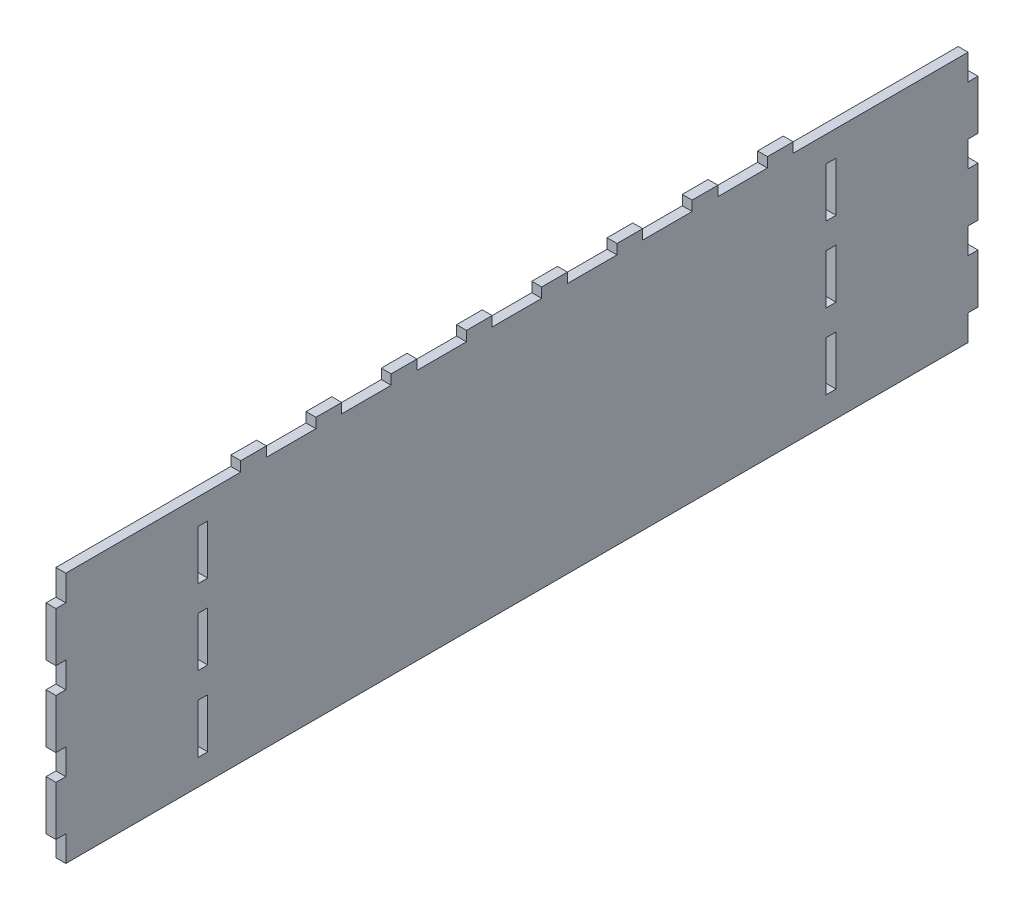
SolidWorks part; units mm, degrees
material "ENPH 253 Hardboard"
ref_plane "Front Plane" through (0, 0, 0) normal (0, 0, 1) x (1, 0, 0)
ref_plane "Top Plane" through (0, 0, 0) normal (0, 1, 0) x (1, 0, 0)
ref_plane "Right Plane" through (0, 0, 0) normal (1, 0, 0) x (0, 0, -1)
sketch "Sketch1" plane through (0, 0, 0) normal (1, 0, 0) x (0, 0, -1)
  line L1 (-139.7, 38.1) -> (139.7, 38.1)
  line L2 (-139.7, 38.1) -> (-139.7, -38.1)
  line L3 (-139.7, -38.1) -> (139.7, -38.1)
  line L4 (139.7, 38.1) -> (139.7, -38.1)
  line L5 (-139.7, 38.1) -> (139.7, -38.1) construction
  line L6 (-139.7, -38.1) -> (139.7, 38.1) construction
  point P0 (0, 0)
  dimension "D1" = 279.4
  dimension "D2" = 76.2
extrude "Boss-Extrude1" add sketch "Sketch1" against normal blind 3 contours L2 L3 L4 L1
sketch "Sketch3" plane through (-3, 0, 0) normal (-1, 0, 0) x (0, 0, 1)
  line L9 (-139.7, 38.1) -> (-136.7, 38.1)
  line L10 (-139.7, 38.1) -> (-139.7, 30.3)
  line L11 (-139.7, 30.3) -> (-136.7, 30.3)
  line L12 (-136.7, 38.1) -> (-136.7, 30.3)
  dimension "D9" = 7.8
  dimension "D10" = 3
extrude "Cut-Extrude1" cut sketch "Sketch3" against normal through all
pattern_linear "LPattern1" count 4 spacing 22.8 along (0, -1, 0) of "Cut-Extrude1"
mirror "Mirror1" about plane through (0, 0, 0) normal (0, 0, 1) of "LPattern1"
sketch "Sketch4" plane through (0, 0, 0) normal (1, 0, 0) x (0, 0, -1)
  line L1 (-96.7, 30.3) -> (-93.7, 30.3)
  line L2 (-96.7, 30.3) -> (-96.7, 15.3)
  line L3 (-96.7, 15.3) -> (-93.7, 15.3)
  line L4 (-93.7, 30.3) -> (-93.7, 15.3)
  line L5 (-136.7, 38.1) -> (136.7, 38.1) construction
  line L6 (-136.7, 30.3) -> (-136.7, 38.1) construction
  dimension "D1" = 40
  dimension "D2" = 3
  dimension "D3" = 7.8
  dimension "D4" = 15
extrude "Cut-Extrude2" cut sketch "Sketch4" against normal blind 10
pattern_linear "LPattern2" count 3 spacing 22.8 along (0, -1, 0) of "Cut-Extrude2"
mirror "Mirror2" about plane through (0, 0, 0) normal (0, 0, 1) of "LPattern2"
sketch "Sketch5" plane through (0, 38.1, 0) normal (0, 1, 0) x (1, 0, 0)
  line L0 (-3, -136.7) -> (-3, 136.7) construction
  line L1 (-3, -75.9) -> (0, -75.9)
  line L2 (-3, -75.9) -> (-3, -83.7)
  line L3 (-3, -83.7) -> (0, -83.7)
  line L4 (0, -75.9) -> (0, -83.7)
  line L5 (0, -136.7) -> (-3, -136.7) construction
  dimension "D1" = 53
  dimension "D2" = 7.8
  dimension "D3" = 3
extrude "Boss-Extrude2" add sketch "Sketch5" along normal blind 3
pattern_linear "LPattern3" count 8 spacing 22.8 along (0, 0, -1) of "Boss-Extrude2"
